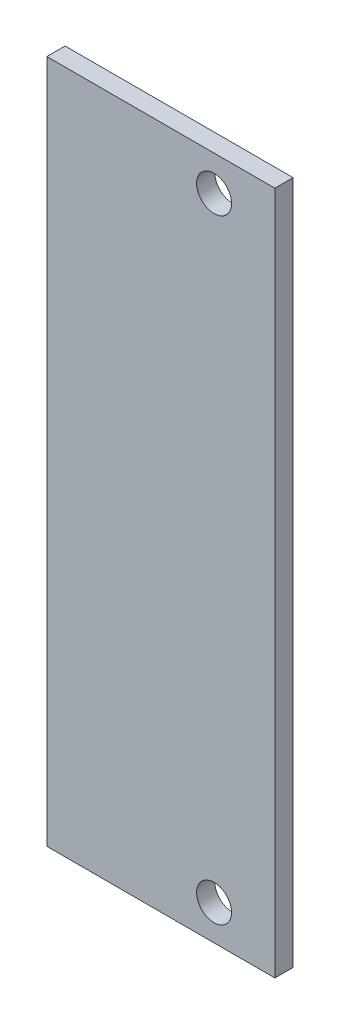
SolidWorks part; units mm, degrees
ref_plane "正面" through (0, 0, 0) normal (1, 0, 0) x (0, 1, 0)
ref_plane "平面" through (0, 0, 0) normal (0, 0, 1) x (0, 1, 0)
ref_plane "右側面" through (0, 0, 0) normal (0, 1, 0) x (-1, 0, 0)
sketch "ｽｹｯﾁ1" plane through (0, 0, 0) normal (0, 0, 1) x (0, 1, 0)
  line L0 (22.5, 8) -> (22.5, 0) construction
  line L1 (0, 0) -> (45, 0)
  line L2 (0, 0) -> (0, 8)
  line L3 (0, 8) -> (45, 8)
  line L4 (45, 0) -> (45, 8)
  line L5 (0, 6) -> (4.6, 6) construction
  line L6 (0, 6) -> (0, 2) construction
  line L7 (0, 2) -> (4.6, 2) construction
  line L8 (4.6, 6) -> (4.6, 2) construction
  line L10 (4.6, 4) -> (3.45, 5.9919) construction
  line L11 (3.45, 5.9919) -> (1.15, 5.9919) construction
  line L12 (1.15, 5.9919) -> (0, 4) construction
  line L13 (0, 4) -> (1.15, 2.0081) construction
  line L14 (1.15, 2.0081) -> (3.45, 2.0081) construction
  line L15 (3.45, 2.0081) -> (4.6, 4) construction
  circle A2 centre (2.3, 4) radius 1.9919 construction
  circle A3 centre (2.3, 4) radius 1.15
  circle A4 centre (42.7, 4) radius 1.15
  dimension "D6" = 4.6
  dimension "D7" = 2.3
  dimension "D1" = 8
  dimension "D2" = 45
  dimension "D3" = 4.6
  dimension "D4" = 4
  dimension "D5" = 2
extrude "ﾎﾞｽ - 押し出し1" add sketch "ｽｹｯﾁ1" against normal blind 1.2
sketch "ｽｹｯﾁ3" plane through (-8, 0, 0) normal (-1, 0, 0) x (0, -1, 0)
  line L1 (-45, 0) -> (0, 0)
  line L2 (-45, 0) -> (-45, -1.2)
  line L3 (-45, -1.2) -> (0, -1.2)
  line L4 (0, 0) -> (0, -1.2)
extrude "ﾎﾞｽ - 押し出し2" add sketch "ｽｹｯﾁ3" along normal blind 7
sketch "ｽｹｯﾁ4" plane through (0, 0, -1.2) normal (0, 0, -1) x (1, 0, 0)
  line L1 (0, 0) -> (-8, 0)
  line L2 (0, 0) -> (0, -4.6)
  line L3 (0, -4.6) -> (-8, -4.6)
  line L4 (-8, 0) -> (-8, -4.6)
  line L5 (0, -45) -> (-8, -45)
  line L6 (0, -45) -> (0, -40.4)
  line L7 (0, -40.4) -> (-8, -40.4)
  line L8 (-8, -45) -> (-8, -40.4)
  dimension "D1" = 8
  dimension "D2" = 4.6
  dimension "D3" = 4.6
  dimension "D4" = 8
